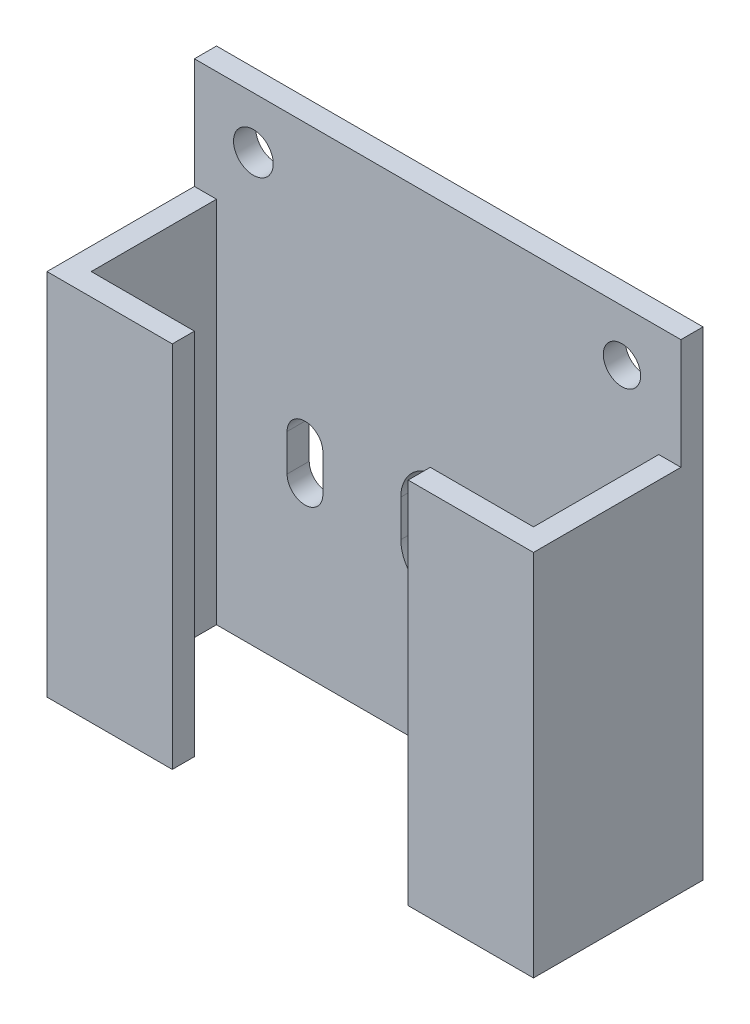
SolidWorks part; units mm, degrees
ref_plane "Front Plane" through (0, 0, 0) normal (0, 0, 1) x (1, 0, 0)
ref_plane "Top Plane" through (0, 0, 0) normal (0, 1, 0) x (1, 0, 0)
ref_plane "Right Plane" through (0, 0, 0) normal (1, 0, 0) x (0, 0, -1)
sketch "Sketch1" plane through (0, 0, 0) normal (1, 0, 0) x (0, 0, -1)
  line L0 (0, 0) -> (0, -65)
  line L1 (0, -65) -> (-23, -65)
  line L2 (-23, -65) -> (-23, 0)
  line L3 (-23, 0) -> (0, 0)
  dimension "D1" = 65
  dimension "D2" = 23
extrude "Boss-Extrude1" add sketch "Sketch1" against normal blind 66
sketch "Sketch2" plane through (0, 0, 0) normal (0, 1, 0) x (1, 0, 0)
  line L0 (-33, 0) -> (-33, -23) construction
  line L1 (-66, 0) -> (0, 0) construction
  line L2 (-66, -23) -> (0, -23) construction
  line L3 (-66, -11.5) -> (0, -11.5) construction
  line L4 (-66, 0) -> (-66, -23) construction
  line L5 (0, 0) -> (0, -23) construction
  line L7 (-63, -20) -> (-3, -20)
  line L8 (-63, -20) -> (-63, -3)
  line L9 (-63, -3) -> (-3, -3)
  line L10 (-3, -20) -> (-3, -3)
  line L11 (-63, -20) -> (-3, -3) construction
  line L12 (-63, -3) -> (-3, -20) construction
  point P12 (-33, -11.5)
  point P17 (-3, -11.5)
  point P18 (-63, -11.5)
  dimension "D1" = 3
  dimension "D2" = 3
  dimension "D3" = 3
  dimension "D4" = 3
extrude "Cut-Extrude1" cut sketch "Sketch2" against normal through all
sketch "Sketch3" plane through (0, 0, 23) normal (0, 0, 1) x (1, 0, 0)
  line L0 (-66, 0) -> (0, 0) construction
  line L1 (-49, 0) -> (-17, 0)
  line L2 (-49, 0) -> (-49, -65)
  line L3 (-49, -65) -> (-17, -65)
  line L4 (-17, 0) -> (-17, -65)
  line L5 (-66, 0) -> (-66, -65) construction
  line L6 (0, 0) -> (0, -65) construction
  dimension "D1" = 17
  dimension "D2" = 17
  dimension "D3" = 32
  dimension "D4" = 65
extrude "Cut-Extrude2" cut sketch "Sketch3" against normal up to next
sketch "Sketch5" plane through (0, 0, 0) normal (0, 0, -1) x (-1, 0, 0)
  line L0 (33, -65) -> (33, 0) construction
  line L1 (66, -65) -> (0, -65) construction
  line L2 (66, 0) -> (0, 0) construction
  line L3 (0, -32.5) -> (66, -32.5) construction
  line L4 (0, -65) -> (0, 0) construction
  line L5 (66, -65) -> (66, 0) construction
  line L6 (66, -37.5) -> (0, -37.5) construction
  line L7 (33, -37.5) -> (33, -42.5) construction
  line L8 (38, -37.5) -> (38, -42.5)
  line L9 (28, -37.5) -> (28, -42.5)
  line L10 (15, -37.5) -> (15, -42.5) construction
  line L11 (17.4772, -37.5) -> (17.4772, -42.5)
  line L12 (12.5228, -37.5) -> (12.5228, -42.5)
  line L13 (51, -37.5) -> (51, -42.5) construction
  line L14 (53.4248, -37.5) -> (53.4248, -42.5)
  line L15 (48.5752, -37.5) -> (48.5752, -42.5)
  circle A1 centre (8, -7) radius 2.5306
  circle A2 centre (58, -7) radius 2.6928
  arc A5 (38, -37.5) -> (28, -37.5) centre (33, -37.5) ccw
  arc A6 (28, -42.5) -> (38, -42.5) centre (33, -42.5) ccw
  arc A7 (17.4772, -37.5) -> (12.5228, -37.5) centre (15, -37.5) ccw
  arc A8 (12.5228, -42.5) -> (17.4772, -42.5) centre (15, -42.5) ccw
  arc A9 (53.4248, -37.5) -> (48.5752, -37.5) centre (51, -37.5) ccw
  arc A10 (48.5752, -42.5) -> (53.4248, -42.5) centre (51, -42.5) ccw
  point P22 (15, -40)
  point P24 (33, -40)
  point P34 (51, -40)
  dimension "D2" = 5
  dimension "D7" = 5
  dimension "D8" = 18
  dimension "D1" = 10
  dimension "D3" = 8
  dimension "D4" = 8
  dimension "D5" = 7
  dimension "D6" = 7
  dimension "D9" = 5
  dimension "D10" = 18
  dimension "D11" = 5
extrude "Cut-Extrude3" cut sketch "Sketch5" against normal up to next
sketch "Sketch6" plane through (0, 0, 23) normal (0, 0, 1) x (1, 0, 0)
  line L0 (-49, 0) -> (-49, -65) construction
  line L1 (-66, 0) -> (-49, 0)
  line L2 (-66, 0) -> (-66, -15)
  line L3 (-66, -15) -> (-49, -15)
  line L4 (-49, 0) -> (-49, -15)
  line L5 (0, 0) -> (0, -65) construction
  line L6 (-17, 0) -> (0, 0)
  line L7 (-17, 0) -> (-17, -15)
  line L8 (-17, -15) -> (0, -15)
  line L9 (0, 0) -> (0, -15)
  dimension "D1" = 15
  dimension "D2" = 15
  dimension "D3" = 17
  dimension "D4" = 17
extrude "Cut-Extrude4" cut sketch "Sketch6" against normal up to surface (20 mm away) up to face at (-10.5306, -7, 3)
